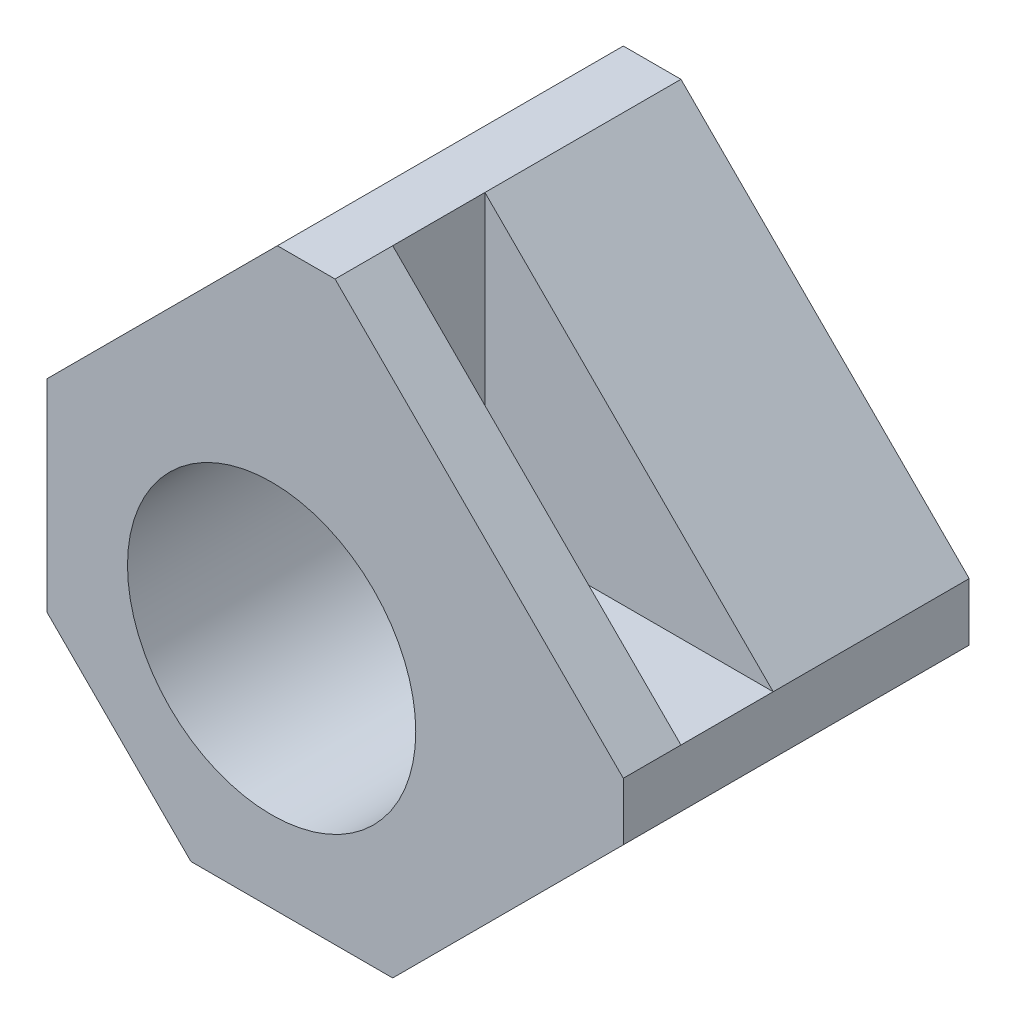
SolidWorks part; units mm, degrees
ref_plane "Plan de face" through (0, 0, 0) normal (0, 0, 1) x (1, 0, 0)
ref_plane "Plan de dessus" through (0, 0, 0) normal (0, 1, 0) x (1, 0, 0)
ref_plane "Plan de droite" through (0, 0, 0) normal (1, 0, 0) x (0, 0, -1)
sketch "Esquisse1" plane through (0, 0, 0) normal (0, 0, 1) x (1, 0, 0)
  line L1 (0, 0) -> (20, 0)
  line L2 (0, 0) -> (0, 20)
  line L3 (0, 20) -> (20, 20)
  line L4 (20, 0) -> (20, 20)
  dimension "D1" = 20
  dimension "D2" = 20
extrude "Boss.-Extru.1" add sketch "Esquisse1" along normal blind 12
chamfer "Chanfrein1" distance 10 angle 45 1 edges at (20, 20, 6)
sketch "Esquisse2" plane through (0, 0, 12) normal (0, 0, 1) x (1, 0, 0)
  line L0 (10, 20) -> (10, 10)
  line L1 (10, 10) -> (20, 10)
  line L2 (20, 10) -> (10, 20)
extrude "Enlèv. mat.-Extru.1" cut sketch "Esquisse2" against normal blind 3.2 from offset 2 offset against normal yes
sketch "Esquisse3" plane through (0, 0, 0) normal (0, 0, -1) x (-1, 0, 0)
  line L0 (-10, 0) -> (-10, 20) construction
  line L1 (0, 0) -> (-20, 0) construction
  line L2 (-20, 10) -> (0, 10) construction
  line L3 (0, 20) -> (0, 0) construction
  circle A0 centre (-7.8, 7.8) radius 2.2
  dimension "D1" = 4.4
extrude "Enlèv. mat.-Extru.2" cut sketch "Esquisse3" against normal through all
sketch "Esquisse4" plane through (0, 0, 12) normal (0, 0, 1) x (1, 0, 0)
  circle A0 centre (7.8, 7.8) radius 5
  dimension "D1" = 10
extrude "Enlèv. mat.-Extru.3" cut sketch "Esquisse4" against normal blind 10.5
chamfer "Chanfrein2" distance 5 angle 45 1 edges at (0, 0, 6)
chamfer "Chanfrein3" distance 8 angle 45 2 edges at (20, 0, 6) (0, 20, 6)
